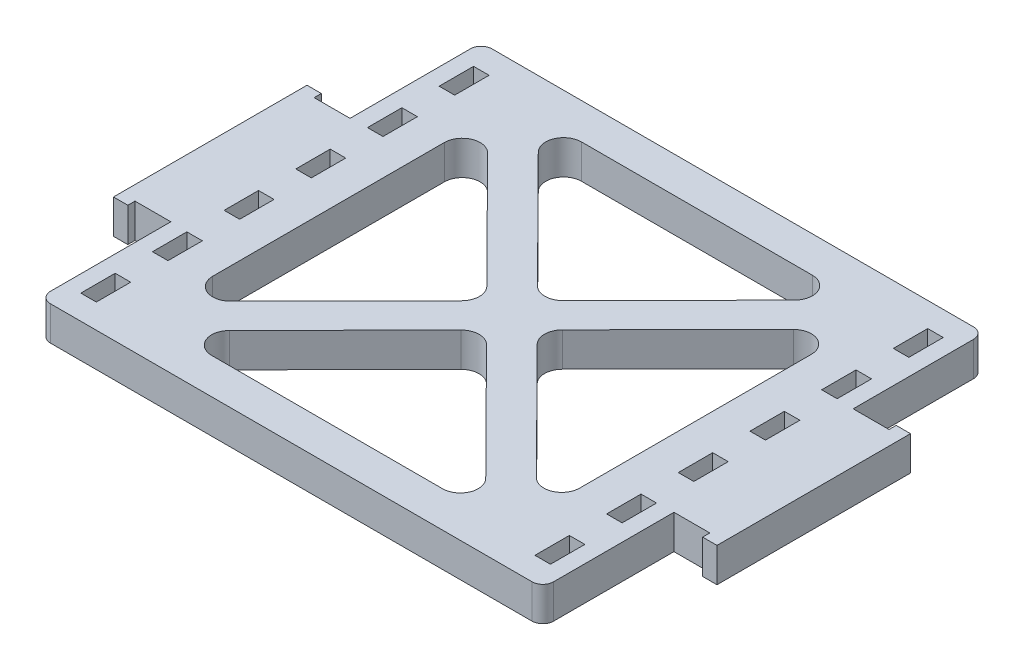
SolidWorks part; units mm, degrees
ref_plane "Front Plane" through (0, 0, 0) normal (0, 0, 1) x (1, 0, 0)
ref_plane "Top Plane" through (0, 0, 0) normal (0, 1, 0) x (1, 0, 0)
ref_plane "Right Plane" through (0, 0, 0) normal (1, 0, 0) x (0, 0, -1)
sketch "Sketch1" plane through (0, 0, 0) normal (0, 1, 0) x (1, 0, 0)
  line L0 (0, 39.116) -> (0, -39.116) construction
  line L1 (-44.577, 39.116) -> (44.577, 39.116)
  line L2 (-44.577, 39.116) -> (-44.577, -39.116)
  line L3 (-44.577, -39.116) -> (44.577, -39.116)
  line L4 (44.577, 39.116) -> (44.577, -39.116)
  line L5 (-44.577, 15.875) -> (-50.927, 15.875)
  line L6 (-44.577, 15.875) -> (-44.577, -15.875)
  line L7 (-44.577, -15.875) -> (-50.927, -15.875)
  line L8 (-50.927, 15.875) -> (-50.927, -15.875)
  line L9 (44.577, -15.875) -> (50.927, -15.875)
  line L10 (50.927, 15.875) -> (50.927, -15.875)
  line L11 (44.577, 15.875) -> (50.927, 15.875)
  line L12 (44.577, 15.875) -> (44.577, -15.875)
  point P4 (0, 39.116)
  point P6 (-44.577, 0)
  point P11 (-50.927, 0)
  dimension "D1" = 89.154
  dimension "D2" = 78.232
  dimension "D3" = 6.35
  dimension "D4" = 31.75
extrude "Boss-Extrude1" add sketch "Sketch1" along normal mid plane 6.0452 contours L0 L1 L2 L3 | L5 L8 L7 L2 | L1 L0 L3 L4 | L11 L4 L9 L10 region at (22.2885, 0, 0) region at (-22.2885, 0, 0) region at (-47.752, 0, 0) region at (47.752, 0, 0)
sketch "Sketch4" plane through (0, 3.0226, 0) normal (0, 1, 0) x (1, 0, 0)
  line L0 (-41.612, -34.798) -> (-38.862, -34.798)
  line L1 (-41.612, -34.798) -> (-41.612, -28.702)
  line L2 (-41.612, -28.702) -> (-38.862, -28.702)
  line L3 (-38.862, -34.798) -> (-38.862, -28.702)
  line L5 (-44.577, -39.116) -> (44.577, -39.116) construction
  line L6 (-41.612, -22.098) -> (-38.862, -22.098)
  line L7 (-38.862, -22.098) -> (-38.862, -16.002)
  line L8 (-41.612, -16.002) -> (-38.862, -16.002)
  line L9 (-41.612, -22.098) -> (-41.612, -16.002)
  line L10 (-41.612, -9.398) -> (-38.862, -9.398)
  line L11 (-38.862, -9.398) -> (-38.862, -3.302)
  line L12 (-41.612, -3.302) -> (-38.862, -3.302)
  line L13 (-41.612, -9.398) -> (-41.612, -3.302)
  line L14 (-41.612, 3.302) -> (-38.862, 3.302)
  line L15 (-38.862, 3.302) -> (-38.862, 9.398)
  line L16 (-41.612, 9.398) -> (-38.862, 9.398)
  line L17 (-41.612, 3.302) -> (-41.612, 9.398)
  line L18 (-41.612, 16.002) -> (-38.862, 16.002)
  line L19 (-38.862, 16.002) -> (-38.862, 22.098)
  line L20 (-41.612, 22.098) -> (-38.862, 22.098)
  line L21 (-41.612, 16.002) -> (-41.612, 22.098)
  line L22 (-41.612, 28.702) -> (-38.862, 28.702)
  line L23 (-38.862, 28.702) -> (-38.862, 34.798)
  line L24 (-41.612, 34.798) -> (-38.862, 34.798)
  line L25 (-41.612, 28.702) -> (-41.612, 34.798)
  line L50 (-41.612, -34.798) -> (-41.612, -22.098) construction
  line L51 (41.612, 28.702) -> (41.612, 34.798)
  line L52 (0, 39.116) -> (0, -39.116) construction
  line L53 (-44.577, 39.116) -> (44.577, 39.116) construction
  line L54 (41.612, 34.798) -> (38.862, 34.798)
  line L55 (38.779, -22.098) -> (41.529, -22.098) [skipped]
  line L56 (41.529, -22.098) -> (41.529, -16.002) [skipped]
  line L57 (38.779, -16.002) -> (41.529, -16.002) [skipped]
  line L58 (38.779, -22.098) -> (38.779, -16.002) [skipped]
  line L59 (38.779, -9.398) -> (41.529, -9.398) [skipped]
  line L60 (41.529, -9.398) -> (41.529, -3.302) [skipped]
  line L61 (38.779, -3.302) -> (41.529, -3.302) [skipped]
  line L62 (38.779, -9.398) -> (38.779, -3.302) [skipped]
  line L63 (38.779, 3.302) -> (41.529, 3.302) [skipped]
  line L64 (41.529, 3.302) -> (41.529, 9.398) [skipped]
  line L65 (38.779, 9.398) -> (41.529, 9.398) [skipped]
  line L66 (38.779, 3.302) -> (38.779, 9.398) [skipped]
  line L67 (38.779, 16.002) -> (41.529, 16.002) [skipped]
  line L68 (41.529, 16.002) -> (41.529, 22.098) [skipped]
  line L69 (38.779, 22.098) -> (41.529, 22.098) [skipped]
  line L70 (38.779, 16.002) -> (38.779, 22.098) [skipped]
  line L71 (38.779, 28.702) -> (41.529, 28.702) [skipped]
  line L72 (41.529, 28.702) -> (41.529, 34.798) [skipped]
  line L73 (38.779, 34.798) -> (41.529, 34.798) [skipped]
  line L74 (38.779, 28.702) -> (38.779, 34.798) [skipped]
  line L75 (38.779, -34.798) -> (41.529, -34.798) [skipped]
  line L76 (41.529, -34.798) -> (41.529, -28.702) [skipped]
  line L77 (38.779, -28.702) -> (41.529, -28.702) [skipped]
  line L78 (38.779, -34.798) -> (38.779, -28.702) [skipped]
  line L79 (38.862, 28.702) -> (38.862, 34.798)
  line L80 (41.612, 28.702) -> (38.862, 28.702)
  line L81 (41.612, 16.002) -> (41.612, 22.098)
  line L82 (41.612, 22.098) -> (38.862, 22.098)
  line L83 (38.862, 16.002) -> (38.862, 22.098)
  line L84 (41.612, 16.002) -> (38.862, 16.002)
  line L85 (41.612, 3.302) -> (41.612, 9.398)
  line L86 (41.612, 9.398) -> (38.862, 9.398)
  line L87 (38.862, 3.302) -> (38.862, 9.398)
  line L88 (41.612, 3.302) -> (38.862, 3.302)
  line L89 (41.612, -9.398) -> (41.612, -3.302)
  line L90 (41.612, -3.302) -> (38.862, -3.302)
  line L91 (38.862, -9.398) -> (38.862, -3.302)
  line L92 (41.612, -9.398) -> (38.862, -9.398)
  line L93 (41.612, -22.098) -> (41.612, -16.002)
  line L94 (41.612, -16.002) -> (38.862, -16.002)
  line L95 (38.862, -22.098) -> (38.862, -16.002)
  line L96 (41.612, -22.098) -> (38.862, -22.098)
  line L97 (41.612, -34.798) -> (41.612, -28.702)
  line L98 (41.612, -28.702) -> (38.862, -28.702)
  line L99 (38.862, -34.798) -> (38.862, -28.702)
  line L100 (41.612, -34.798) -> (38.862, -34.798)
  dimension "D1" = 6.096
  dimension "D2" = 2.75
  dimension "D3" = 38.862
  dimension "D4" = 4.318
  dimension "D5" = 12.7
  dimension "D7" = 6
  dimension "D8" = 2
extrude "Cut-Extrude2" cut sketch "Sketch4" against normal blind 6.0452
sketch "Sketch5" plane through (0, 3.0226, 0) normal (0, 1, 0) x (1, 0, 0)
  line L0 (-50.927, 15.875) -> (-50.927, -15.875) construction
  line L1 (-53.467, 17.145) -> (-50.927, 17.145)
  line L2 (-53.467, 17.145) -> (-53.467, -17.145)
  line L3 (-53.467, -17.145) -> (-50.927, -17.145)
  line L4 (-50.927, 17.145) -> (-50.927, -17.145)
  line L8 (0, 39.116) -> (0, -39.116) construction
  line L9 (-44.577, 39.116) -> (44.577, 39.116) construction
  line L10 (-44.577, -39.116) -> (44.577, -39.116) construction
  line L11 (53.467, -17.145) -> (50.927, -17.145)
  line L12 (50.927, 17.145) -> (50.927, -17.145)
  line L13 (53.467, 17.145) -> (50.927, 17.145)
  line L14 (53.467, 17.145) -> (53.467, -17.145)
  line L15 (-44.577, 15.875) -> (-50.927, 15.875) construction
  point P6 (-53.467, 0)
  dimension "D1" = 1.27
  dimension "D2" = 2.54
extrude "Boss-Extrude2" add sketch "Sketch5" against normal blind 6.0452
sketch "Sketch6" plane through (0, 3.0226, 0) normal (0, 1, 0) x (1, 0, 0)
  line L0 (-44.577, 39.116) -> (44.577, 39.116) construction
  line L1 (-38.862, 39.116) -> (38.862, 39.116) construction
  line L2 (-38.862, 39.116) -> (-38.862, -39.116) construction
  line L3 (-38.862, -39.116) -> (38.862, -39.116) construction
  line L4 (38.862, 39.116) -> (38.862, -39.116) construction
  line L5 (-44.577, -39.116) -> (44.577, -39.116) construction
  line L6 (38.862, -28.702) -> (38.862, -34.798) construction
  line L7 (-32.512, 32.766) -> (32.512, 32.766)
  line L8 (-38.862, 28.702) -> (-38.862, 34.798) construction
  line L9 (-38.862, 39.116) -> (38.862, -39.116) construction
  line L10 (38.862, 39.116) -> (-38.862, -39.116) construction
  line L11 (32.512, 32.766) -> (32.512, -32.766)
  line L12 (-32.512, -32.766) -> (32.512, -32.766)
  line L13 (-32.512, 32.766) -> (-32.512, -32.766)
  line L14 (-41.1144, 36.8783) -> (36.6096, -41.3537)
  line L15 (36.6096, 41.3537) -> (-41.1144, -36.8783)
  line L16 (-36.6096, 41.3537) -> (41.1144, -36.8783)
  line L17 (41.1144, 36.8783) -> (-36.6096, -41.3537)
  dimension "D1" = 6.35
  dimension "D2" = 3.175
  dimension "D3" = 3.175
extrude "Cut-Extrude3" cut sketch "Sketch6" against normal through all contours L7 L16 L15 | L15 L14 L13 | L14 L17 L12 | L11 L17 L16 region at (0, 3.0226, -23.3456) region at (-23.1665, 3.0226, 0) region at (23.1665, 3.0226, 0) region at (0, 3.0226, 23.3456)
fillet "Fillet1" radius 3.175 12 edges at (28.0777, 0, -32.766) (-28.0777, 0, -32.766) (0, 0, -4.5048) (-32.512, 0, -28.2197) (-4.4756, 0, 0) (-32.512, 0, 28.2197) (-28.0777, 0, 32.766) (0, 0, 4.5048) (28.0777, 0, 32.766) (4.4756, 0, 0) (32.512, 0, -28.2197) (32.512, 0, 28.2197)
fillet "Fillet2" radius 1.905 4 edges at (44.577, 0, 39.116) (44.577, 0, -39.116) (-44.577, 0, 39.116) (-44.577, 0, -39.116)
